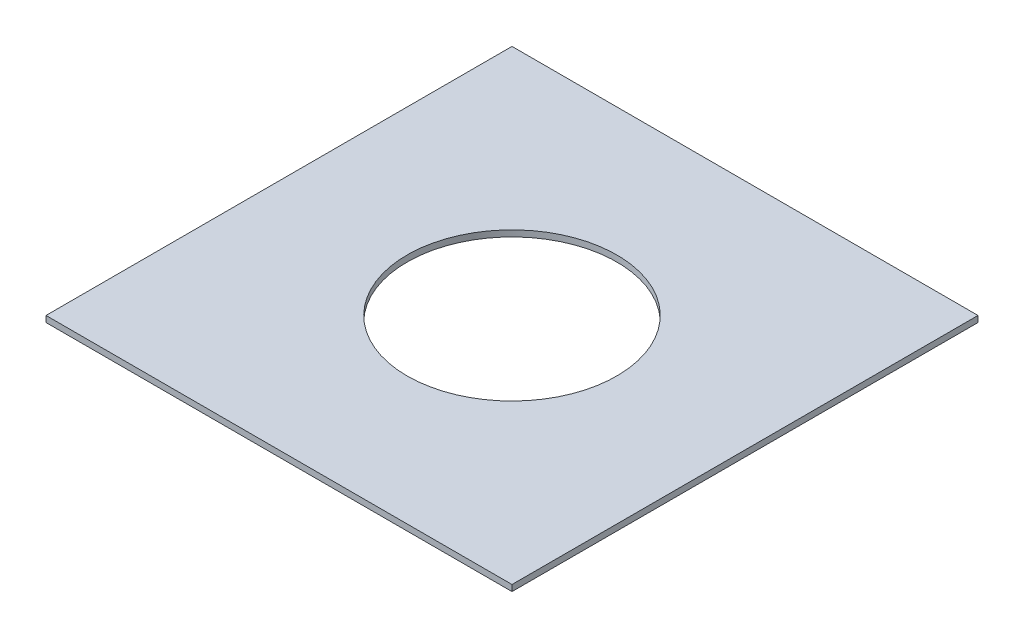
SolidWorks part; units mm, degrees
material "PTFE (general)"
ref_plane "Front Plane" through (0, 0, 0) normal (0, 0, 1) x (1, 0, 0)
ref_plane "Top Plane" through (0, 0, 0) normal (0, 1, 0) x (1, 0, 0)
ref_plane "Right Plane" through (0, 0, 0) normal (1, 0, 0) x (0, 0, -1)
sketch "Sketch1" plane through (0, 0, 0) normal (0, 1, 0) x (1, 0, 0)
  line L12 (17.5573, 30.5402) -> (17.5573, -29.4598)
  line L13 (17.5573, -29.4598) -> (77.5573, -29.4598)
  line L14 (77.5573, -29.4598) -> (77.5573, 30.5402)
  line L16 (17.5573, 30.5402) -> (77.5573, 30.5402)
  circle A2 centre (47.5573, 0.5402) radius 13.5
  circle A3 centre (47.5573, 0.5402) radius 13.5
  point P2 (0, 0)
  point P4 (17.5573, 30.5402)
  point P6 (77.5573, -29.4598)
  point P7 (77.5573, 30.5402)
  point P14 (17.5573, -29.4598)
  dimension "D1" = 0
extrude "Boss-Extrude1" add sketch "Sketch1" along normal blind 0.7937
